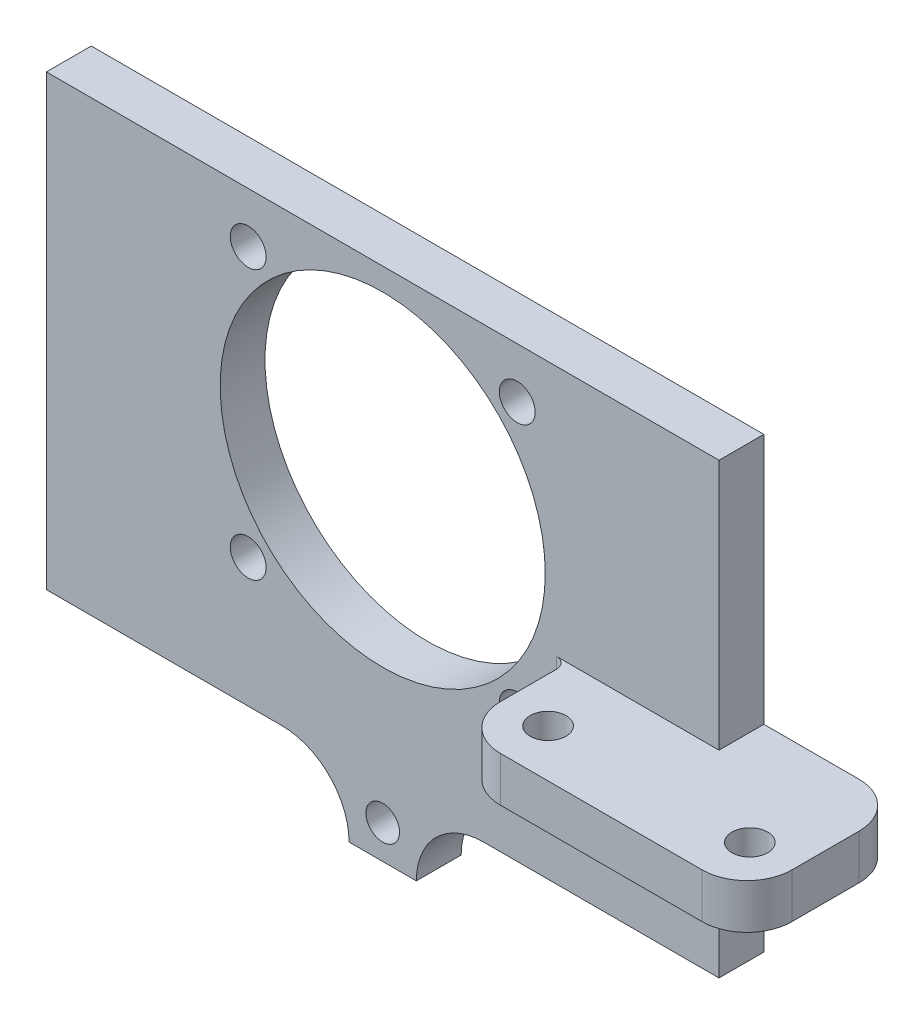
SolidWorks part; units mm, degrees
ref_plane "Płaszczyzna przednia" through (0, 0, 0) normal (0, 0, 1) x (1, 0, 0)
ref_plane "Płaszczyzna górna" through (0, 0, 0) normal (0, 1, 0) x (1, 0, 0)
ref_plane "Płaszczyzna prawa" through (0, 0, 0) normal (1, 0, 0) x (0, 0, -1)
sketch "Sketch1" plane through (0, 0, 0) normal (0, 0, 1) x (1, 0, 0)
  line L1 (0, 0) -> (60, 0)
  line L2 (0, 0) -> (0, 40)
  line L3 (0, 40) -> (60, 40)
  line L4 (60, 0) -> (60, 40)
  line L5 (0, 0) -> (60, 40) construction
  line L6 (0, 40) -> (60, 0) construction
  point P4 (30, 20)
  dimension "D1" = 60
  dimension "D2" = 40
extrude "Boss-Extrude1" add sketch "Sketch1" along normal blind 4
sketch "Sketch4" plane through (0, 0, 4) normal (0, 0, 1) x (1, 0, 0)
  line L0 (0, 40) -> (60, 0) construction
  line L1 (0, 0) -> (60, 40) construction
  line L2 (30, -0.7473) -> (30, 40.7473) construction
  line L3 (60, 40) -> (0, 40) construction
  circle A0 centre (30, 23.5) radius 14.5
  point P10 (30, 20)
  point P16 (30, 20)
  dimension "D1" = 29
  dimension "D2" = 16.5
extrude "Cut-Extrude1" cut sketch "Sketch4" against normal blind 4
sketch "Sketch6" plane through (0, 0, 4) normal (0, 0, 1) x (1, 0, 0)
  circle A0 centre (42, 11.5) radius 1.6
  circle A1 centre (18, 11.5) radius 1.6
  circle A2 centre (18, 35.5) radius 1.6
  circle A3 centre (42, 35.5) radius 1.6
  dimension "D1" = 3.2
  dimension "D2" = 3.2
  dimension "D3" = 3.2
  dimension "D4" = 3.2
extrude "Cut-Extrude2" cut sketch "Sketch6" against normal blind 4
sketch "Sketch7" plane through (0, 0, 4) normal (0, 0, 1) x (1, 0, 0)
  line L0 (56.5, 17.6) -> (62.5, 17.6) construction
  line L1 (46.5, 17.6) -> (72.5, 17.6)
  line L2 (46.5, 17.6) -> (46.5, 13.6)
  line L3 (46.5, 13.6) -> (72.5, 13.6)
  line L4 (72.5, 17.6) -> (72.5, 13.6)
  line L5 (46.5, 17.6) -> (72.5, 13.6) construction
  line L6 (46.5, 13.6) -> (72.5, 17.6) construction
  line L10 (59.5, 13.6) -> (59.5, 17.6) construction
  line L11 (62.5, 17.6) -> (62.5, 20) construction
  point P4 (59.5, 15.6)
  dimension "D1" = 4
  dimension "D2" = 26
  dimension "D3" = 3
extrude "Boss-Extrude3" add sketch "Sketch7" along normal blind 10
sketch "Sketch8" plane through (0, 17.6, 0) normal (0, 1, 0) x (1, 0, 0)
  circle A0 centre (68.5, -9.75) radius 1.6
  circle A1 centre (50.5, -9.75) radius 1.6
extrude "Cut-Extrude3" cut sketch "Sketch8" against normal through all
sketch "Sketch9" plane through (60, 0, 0) normal (1, 0, 0) x (0, 0, -1)
  line L0 (0, 0) -> (0, 40) construction
  line L1 (-4, 13.6) -> (0, 13.6)
  line L2 (-4, 13.6) -> (-4, 17.6)
  line L3 (-4, 17.6) -> (0, 17.6)
  line L4 (0, 13.6) -> (0, 17.6)
  line L5 (-4, 13.6) -> (0, 17.6) construction
  line L6 (-4, 17.6) -> (0, 13.6) construction
  point P4 (-2, 15.6)
extrude "Boss-Extrude4" add sketch "Sketch9" along normal blind 12.5
fillet "Fillet2" radius 4 3 edges at (72.5, 15.6, 14) (46.5, 15.6, 14) (72.5, 15.6, 0)
fillet "Fillet3" radius 1 3 edges at (60, 13.6, 2) (53.25, 13.6, 4) (46.5, 15.6, 4)
sketch "Sketch10" plane through (0, 0, 0) normal (0, -1, 0) x (1, 0, 0)
  line L0 (0, 4) -> (60, 4) construction
  line L1 (33, 4) -> (27, 4)
  line L2 (33, 4) -> (33, 0)
  line L3 (33, 0) -> (27, 0)
  line L4 (27, 4) -> (27, 0)
  line L5 (33, 4) -> (27, 0) construction
  line L6 (33, 0) -> (27, 4) construction
  line L7 (0, 0) -> (60, 0) construction
  line L8 (60, 4) -> (60, 0) construction
  line L9 (0, 4) -> (0, 0) construction
  point P4 (30, 2)
  point P9 (33, 2)
  dimension "D1" = 6
  dimension "D2" = 27
  dimension "D3" = 27
extrude "Boss-Extrude5" add sketch "Sketch10" along normal blind 6
fillet "Fillet4" radius 6 2 edges at (27, 0, 2) (33, 0, 2)
hole_wizard "Ø3.0 (3) Diameter Hole1" positions "Sketch11" profile "Sketch12" hole size "Ø3.0" standard "ANSI Metric" end condition up to next
sketch "Sketch11" plane through (0, 0, 4) normal (0, 0, 1) x (1, 0, 0)
  line L0 (33, -6) -> (27, -6) construction
  point P0 (30, -3)
  dimension "D1" = 3
  dimension "D2" = 3
sketch "Sketch12" plane through (30, -3, 4) normal (1, 0, 0) x (0, -1, 0)
  line L0 (0, 0) -> (0, 4)
  line L1 (0, 4) -> (1.5, 4)
  line L2 (1.5, 4) -> (1.5, 0)
  line L5 (1.5, 0) -> (0, 0)
  line L11 (0, -6.35) -> (0, 107.95) construction
  dimension "Thru Hole Dia." = 3
  dimension "Thru Hole Depth" = 4
